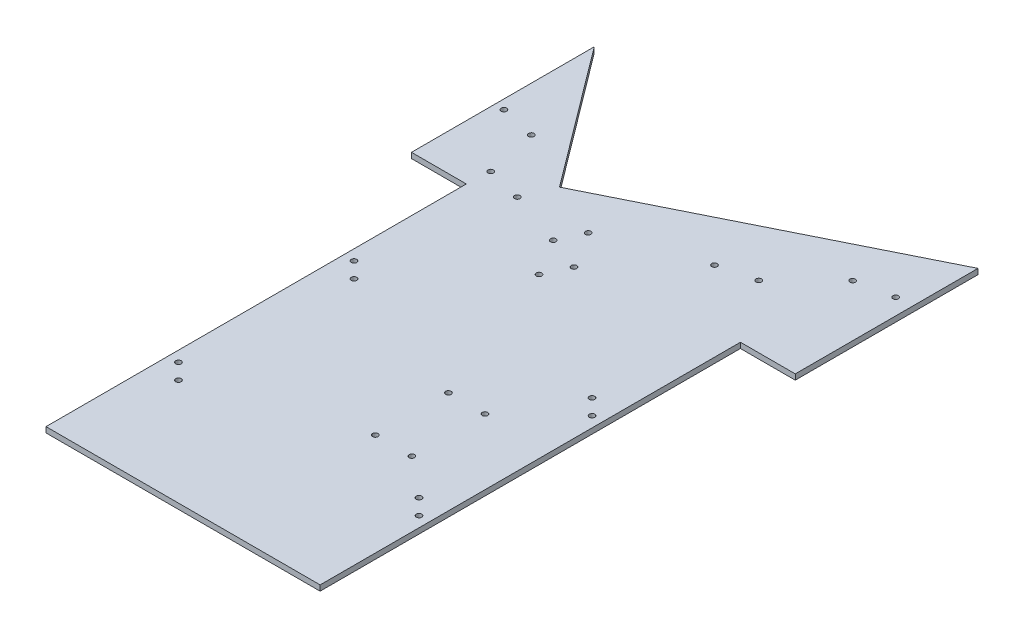
SolidWorks part; units mm, degrees
ref_plane "Front Plane" through (0, 0, 0) normal (0, 0, 1) x (1, 0, 0)
ref_plane "Top Plane" through (0, 0, 0) normal (0, 1, 0) x (1, 0, 0)
ref_plane "Right Plane" through (0, 0, 0) normal (1, 0, 0) x (0, 0, -1)
sketch "Sketch1" plane through (0, 0, 0) normal (0, 1, 0) x (1, 0, 0)
  line L1 (-75, -100) -> (75, -100)
  line L2 (-75, -100) -> (-75, 100)
  line L3 (-75, 100) -> (75, 100)
  line L4 (75, -100) -> (75, 100)
  line L5 (-75, -100) -> (75, 100) construction
  line L6 (-75, 100) -> (75, -100) construction
  circle A0 centre (-69.2426, 62.7961) radius 1.5
  circle A1 centre (-60.7574, 54.3108) radius 1.5
  circle A2 centre (60.7574, 63.0348) radius 1.5
  circle A3 centre (69.2426, 54.5495) radius 1.5
  circle A4 centre (-69.2426, -33.2742) radius 1.5
  circle A5 centre (-60.7574, -41.7595) radius 1.5
  circle A6 centre (60.7574, -31.6419) radius 1.5
  circle A7 centre (69.2426, -40.1271) radius 1.5
  circle A8 centre (19.1, 26.1028) radius 1.5
  circle A10 centre (39.1, -13.8972) radius 1.5
  circle A11 centre (19.1, -13.8972) radius 1.5
  circle A12 centre (39.1, 26.1028) radius 1.5
  point P0 (0, 0)
  dimension "D1" = 150
  dimension "D2" = 200
extrude "Boss-Extrude1" add sketch "Sketch1" along normal blind 3
sketch "Sketch2" plane through (0, 3, 0) normal (0, 1, 0) x (1, 0, 0)
  line L8 (-75, 100) -> (-75, 130)
  line L9 (-75, 130) -> (-105, 130)
  line L10 (-105, 130) -> (-105, 230)
  line L11 (-105, 230) -> (-48, 154)
  line L12 (-48, 154) -> (105, 230)
  line L13 (105, 230) -> (105, 130)
  line L14 (105, 130) -> (75, 130)
  line L15 (75, 130) -> (75, 100)
  line L20 (-75, 100) -> (75, 100)
  circle A0 centre (-12.2136, 106.9838) radius 1.5
  circle A1 centre (-6.1619, 120.0749) radius 1.5
  circle A2 centre (-18.4792, 140.175) radius 1.5
  circle A3 centre (-24.5309, 127.0839) radius 1.5
  circle A4 centre (31.34, 159.4445) radius 1.5
  circle A5 centre (50.7426, 164.2965) radius 1.5
  circle A6 centre (76.5366, 189.8832) radius 1.5
  circle A7 centre (96.1557, 193.7679) radius 1.5
  circle A8 centre (-54.8196, 137.7444) radius 1.5
  circle A9 centre (-74.2221, 142.5964) radius 1.5
  circle A10 centre (-80.4244, 170.9971) radius 1.5
  circle A11 centre (-99.9157, 175.4791) radius 1.5
  dimension "D2" = 100
  dimension "D3" = 27
  dimension "D4" = 30
  dimension "D1" = 30
  dimension "D5" = 24
extrude "Boss-Extrude3" add sketch "Sketch2" against normal blind 3
